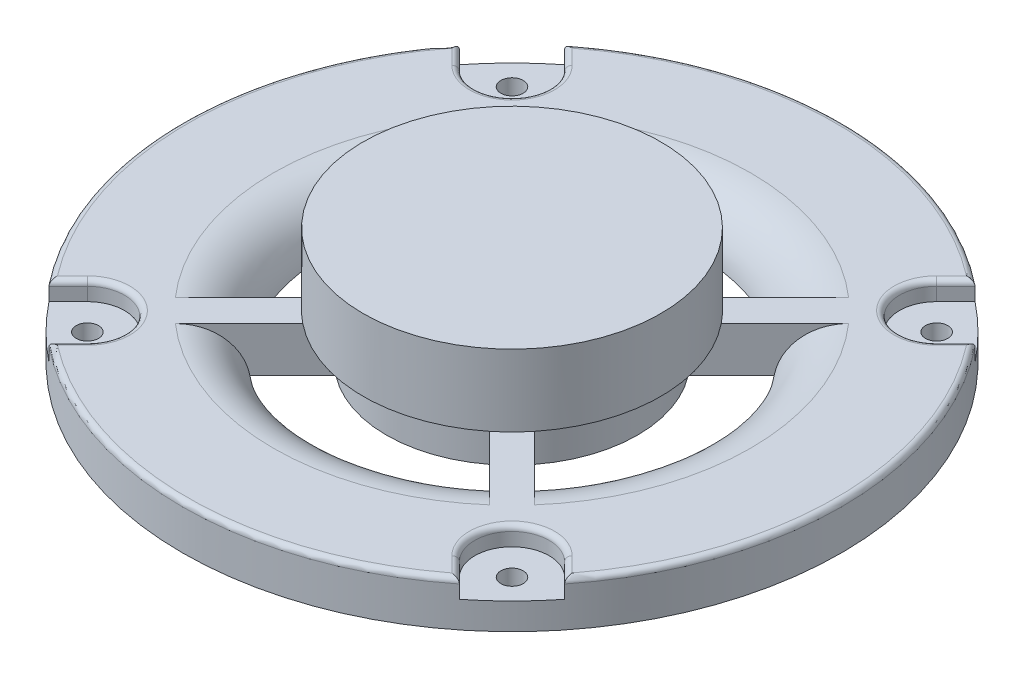
SolidWorks part; units mm, degrees
ref_plane "Спереди" through (0, 0, 0) normal (0, 0, 1) x (1, 0, 0)
ref_plane "Сверху" through (0, 0, 0) normal (0, 1, 0) x (1, 0, 0)
ref_plane "Справа" through (0, 0, 0) normal (1, 0, 0) x (0, 0, -1)
sketch "Эскиз1" plane through (0, 0, 0) normal (0, 1, 0) x (1, 0, 0)
  circle A0 centre (0, 0) radius 62
  circle A1 centre (0, 0) radius 35
  dimension "D1" = 124
  dimension "D2" = 70
extrude "Бобышка-Вытянуть1" add sketch "Эскиз1" along normal blind 8.5
fillet "Скругление1" radius 10 1 edges at (0, 8.5, 35)
sketch "Эскиз2" plane through (0, 8.5, 0) normal (0, 1, 0) x (1, 0, 0)
  line L12 (-14.4488, 18.6915) -> (-29.5475, 33.7902)
  line L16 (-18.6915, 14.4488) -> (-33.7902, 29.5475)
  line L18 (-18.6915, -14.4488) -> (-33.7902, -29.5475)
  line L22 (-14.4488, -18.6915) -> (-29.5475, -33.7902)
  line L24 (14.4488, -18.6915) -> (29.5475, -33.7902)
  line L28 (18.6915, -14.4488) -> (33.7902, -29.5475)
  line L30 (18.6915, 14.4488) -> (33.7902, 29.5475)
  line L34 (14.4488, 18.6915) -> (29.5475, 33.7902)
  arc A1 (29.5475, -33.7902) -> (33.7902, -29.5475) centre (0, 0) ccw
  arc A2 (-33.7902, -29.5475) -> (-29.5475, -33.7902) centre (0, 0) ccw
  arc A3 (-29.5475, 33.7902) -> (-33.7902, 29.5475) centre (0, 0) ccw
  arc A4 (33.7902, 29.5475) -> (29.5475, 33.7902) centre (0, 0) ccw
  arc A5 (14.4488, 18.6915) -> (-14.4488, 18.6915) centre (0, 0) ccw
  arc A6 (-18.6915, 14.4488) -> (-18.6915, -14.4488) centre (0, 0) ccw
  arc A7 (-14.4488, -18.6915) -> (14.4488, -18.6915) centre (0, 0) ccw
  arc A8 (18.6915, -14.4488) -> (18.6915, 14.4488) centre (0, 0) ccw
extrude "Бобышка-Вытянуть2" add sketch "Эскиз2" against normal up to surface (8.5 mm away) up to face at (0, 0, 62)
sketch "Эскиз3" plane through (0, 8.5, 0) normal (0, 1, 0) x (1, 0, 0)
  circle A0 centre (0, 0) radius 28
  dimension "D1" = 56
extrude "Бобышка-Вытянуть3" add sketch "Эскиз3" along normal blind 13.5
sketch "Эскиз4" plane through (0, 8.5, 0) normal (0, 1, 0) x (1, 0, 0)
  line L0 (-48.5101, -38.6106) -> (-44.9013, -35.0018) construction
  line L1 (-35.0018, -44.9013) -> (-38.6106, -48.5101) construction
  line L2 (38.6106, -48.5101) -> (35.0018, -44.9013) construction
  line L3 (44.9013, -35.0018) -> (48.5101, -38.6106) construction
  line L4 (48.5101, 38.6106) -> (44.9013, 35.0018) construction
  line L5 (35.0018, 44.9013) -> (38.6106, 48.5101) construction
  line L6 (-38.6106, 48.5101) -> (-35.0018, 44.9013) construction
  line L7 (-44.9013, 35.0018) -> (-48.5101, 38.6106) construction
  line L8 (-48.5101, -38.6106) -> (-44.9013, -35.0018)
  line L9 (-35.0018, -44.9013) -> (-38.6106, -48.5101)
  line L10 (38.6106, -48.5101) -> (35.0018, -44.9013)
  line L11 (44.9013, -35.0018) -> (48.5101, -38.6106)
  line L12 (48.5101, 38.6106) -> (44.9013, 35.0018)
  line L13 (35.0018, 44.9013) -> (38.6106, 48.5101)
  line L14 (-38.6106, 48.5101) -> (-35.0018, 44.9013)
  line L15 (-44.9013, 35.0018) -> (-48.5101, 38.6106)
  arc A0 (-35.0018, -44.9013) -> (-44.9013, -35.0018) centre (-39.9515, -39.9515) ccw construction
  arc A1 (44.9013, -35.0018) -> (35.0018, -44.9013) centre (39.9515, -39.9515) ccw construction
  arc A2 (35.0018, 44.9013) -> (44.9013, 35.0018) centre (39.9515, 39.9515) ccw construction
  arc A3 (-44.9013, 35.0018) -> (-35.0018, 44.9013) centre (-39.9515, 39.9515) ccw construction
  arc A4 (-35.0018, -44.9013) -> (-44.9013, -35.0018) centre (-39.9515, -39.9515) ccw
  arc A5 (44.9013, -35.0018) -> (35.0018, -44.9013) centre (39.9515, -39.9515) ccw
  arc A6 (35.0018, 44.9013) -> (44.9013, 35.0018) centre (39.9515, 39.9515) ccw
  arc A7 (-44.9013, 35.0018) -> (-35.0018, 44.9013) centre (-39.9515, 39.9515) ccw
  arc A8 (-38.6106, 48.5101) -> (-48.5101, 38.6106) centre (0, 0) ccw
  arc A9 (-48.5101, -38.6106) -> (-38.6106, -48.5101) centre (0, 0) ccw
  arc A10 (38.6106, -48.5101) -> (48.5101, -38.6106) centre (0, 0) ccw
  arc A11 (48.5101, 38.6106) -> (38.6106, 48.5101) centre (0, 0) ccw
extrude "Вырез-Вытянуть1" cut sketch "Эскиз4" against normal blind 3.5
fillet "Скругление2" radius 1 16 edges at (36.8062, 8.5, -46.7057) (46.7057, 8.5, -36.8062) (46.7057, 8.5, 36.8062) (35.0018, 8.5, 35.0018) (-36.8062, 8.5, 46.7057) (-35.0018, 8.5, 35.0018) (-46.7057, 8.5, -36.8062) (-35.0018, 8.5, -35.0018) (0, 8.5, -62) (35.0018, 8.5, -35.0018) (62, 8.5, 0) (36.8062, 8.5, 46.7057) (0, 8.5, 62) (-46.7057, 8.5, 36.8062) (-62, 8.5, 0) (-36.8062, 8.5, -46.7057)
hole_wizard "Отверстие обработанное метчиком M51" positions "Эскиз5" profile "Эскиз6" tap size "M5" standard "ISO"
sketch "Эскиз5" plane through (0, 5, 0) normal (0, 1, 0) x (1, 0, 0)
  point P0 (39.9515, -39.9515)
  point P3 (39.9515, 39.9515)
  point P6 (-39.9515, -39.9515)
  point P9 (-39.9515, 39.9515)
sketch "Эскиз6" plane through (39.9515, 5, 39.9515) normal (1, 0, 0) x (0, 0, 1)
  line L0 (0, 0) -> (0, 15.2618)
  line L1 (0, 15.2618) -> (2.1, 14)
  line L2 (2.1, 14) -> (2.1, 0)
  line L5 (2.1, 0) -> (0, 0)
  line L10 (0, 15.2618) -> (-2.1, 14) construction
  line L11 (0, -6.35) -> (0, 107.95) construction
  dimension "Диаметр сверла" = 4.2
  dimension "Глубина сверла" = 14
  dimension "Угол заточки сверла" = 118
cosmetic thread "Отверстие резьбы1" parameters "D1"=5, "D2"=5
cosmetic thread "Отверстие резьбы2" parameters "D1"=5, "D2"=5
cosmetic thread "Отверстие резьбы3" parameters "D1"=5, "D2"=5
cosmetic thread "Отверстие резьбы4" parameters "D1"=5, "D2"=5
